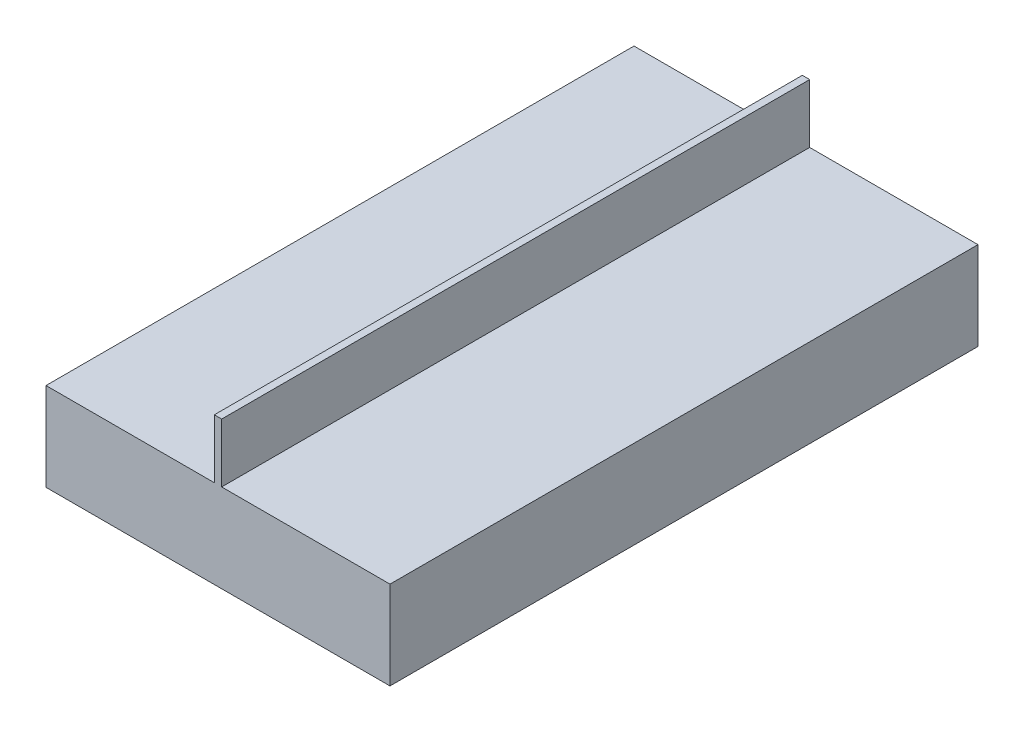
SolidWorks part; units mm, degrees
ref_plane "Front Plane" through (0, 0, 0) normal (0, 0, 1) x (1, 0, 0)
ref_plane "Top Plane" through (0, 0, 0) normal (0, 1, 0) x (1, 0, 0)
ref_plane "Right Plane" through (0, 0, 0) normal (1, 0, 0) x (0, 0, -1)
sketch "Sketch1" plane through (0, 0, 0) normal (0, 0, 1) x (1, 0, 0)
  line L0 (0, 1.2384) -> (0, -6863.7123) construction
  line L1 (-0.5703, 0) -> (6864.3804, 0) construction
  line L3 (-11.7, 3) -> (-0.25, 3)
  line L4 (-11.7, 3) -> (-11.7, -3)
  line L5 (-11.7, -3) -> (11.7, -3)
  line L6 (11.7, 3) -> (11.7, -3)
  line L12 (-0.25, 7) -> (-0.25, 3)
  line L13 (0.25, 7) -> (0.25, 3)
  line L15 (0.25, 3) -> (11.7, 3)
  line L16 (-0.25, 7) -> (0.25, 7)
  point P0 (0, 0)
  dimension "D4" = 23.4
  dimension "D1" = 6
  dimension "D3" = 4
  dimension "D21" = 0.5
extrude "Boss-Extrude1" add sketch "Sketch1" along normal blind 40
sketch "Orientation Sketch" plane through (0, 0, 0) normal (0, 0, -1) x (-1, 0, 0)
  line L0 (11.7, 3) -> (11.7, -3) construction
  line L1 (0.25, 3) -> (11.7, 3) construction
  line L2 (0.25, 7) -> (0.25, 3) construction
  line L3 (-0.25, 7) -> (0.25, 7) construction
  line L4 (-0.25, 3) -> (-0.25, 7) construction
  line L5 (-11.7, 3) -> (-0.25, 3) construction
  line L6 (-11.7, -3) -> (-11.7, 3) construction
  line L7 (11.7, -3) -> (-11.7, -3) construction
  line L8 (11.7, 3) -> (11.7, -3)
  line L9 (0.25, 3) -> (11.7, 3)
  line L10 (0.25, 7) -> (0.25, 3)
  line L11 (-0.25, 7) -> (0.25, 7)
  line L12 (-0.25, 3) -> (-0.25, 7)
  line L13 (-11.7, 3) -> (-0.25, 3)
  line L14 (-11.7, -3) -> (-11.7, 3)
  line L15 (11.7, -3) -> (-11.7, -3)
  point P3 (0, 2)
other "FormTool1"
sketch "Sketch2" plane through (0, 0, 0) normal (0, 0, -1) x (-1, 0, 0)
  circle A0 centre (0, 0) radius 1.5
  dimension "D1" = 3
extrude "Cut-Extrude2" cut sketch "Sketch2" against normal blind 5
thread "Thread1" pitch 0.8 method cut profile "Thread Profile1" start angle 0, offset 0, length 7, pitch 0.8, diameter 3
ref_plane "Plane1" through (1.5, 0, 0) normal (0, -1, 0) x (1, 0, 0)
sketch "Thread Profile1" plane through (1.5, 0, 0) normal (0, -1, 0) x (1, 0, 0)
  line L0 (0, 0) -> (0, 0.8) construction
  line L1 (0, 0) -> (0.433, 0.25)
  line L2 (0.433, 0.25) -> (0.433, 0.35)
  line L3 (0.433, 0.35) -> (0, 0.6)
  line L4 (0.433, 0.3) -> (0, 0.3) construction
  line L11 (0, 0) -> (0, 0.6)
  point P2 (0, 0)
  dimension "Pitch" = 0.8
  dimension "Profile_Angle" = 60
  dimension "Profile_Land" = 0.1
  dimension "Profile_Height" = 0.433
